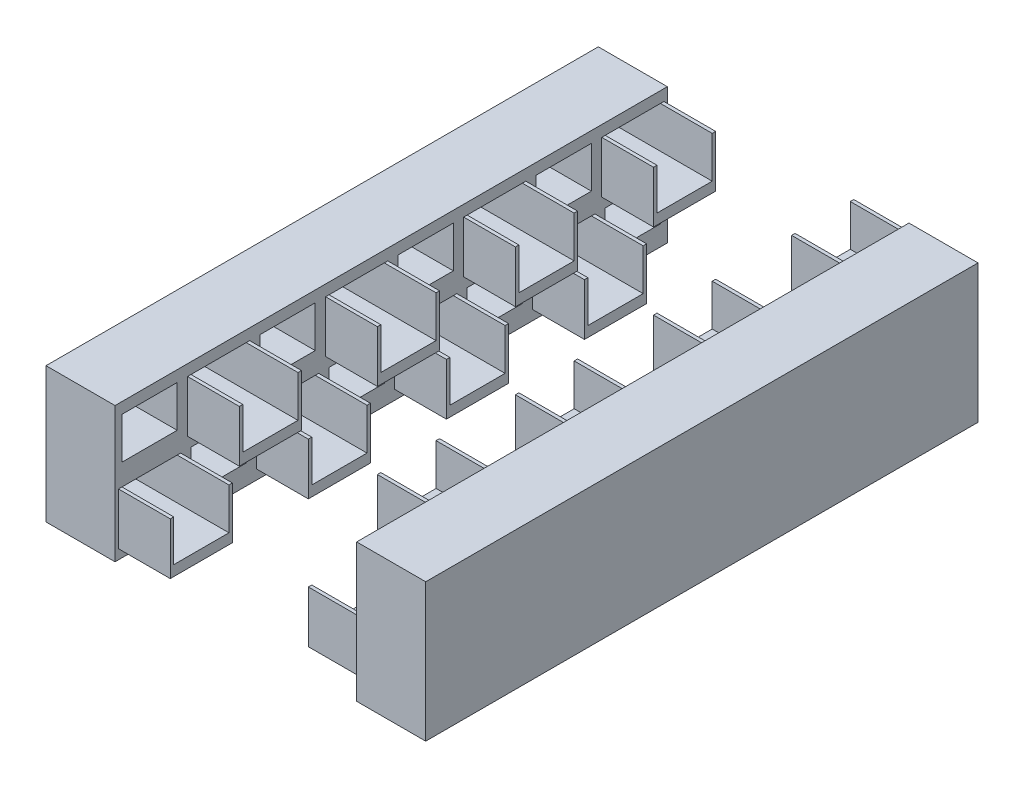
SolidWorks part; units mm, degrees
material "6061-O (SS)"
ref_plane "Alzado" through (0, 0, 0) normal (0, 0, 1) x (1, 0, 0)
ref_plane "Planta" through (0, 0, 0) normal (0, 1, 0) x (1, 0, 0)
ref_plane "Vista lateral" through (0, 0, 0) normal (1, 0, 0) x (0, 0, -1)
sketch "Sketch2" plane through (0, 0, 0) normal (1, 0, 0) x (0, 0, -1)
  line L160 (-3913.0493, 1960.5992) -> (4086.9507, 1960.5992)
  line L161 (-3913.0493, 1960.5992) -> (-3913.0493, 0)
  line L162 (-3913.0493, 0) -> (4086.9507, 0)
  line L163 (4086.9507, 1960.5992) -> (4086.9507, 0)
  line L164 (-3813.0493, 889.2792) -> (-3013.0493, 889.2792)
  line L165 (-3863.0493, 889.2792) -> (-2963.0493, 889.2792)
  line L166 (-3863.0493, 1799.9392) -> (-2963.0493, 1799.9392)
  line L167 (-3863.0493, 1799.9392) -> (-3863.0493, 1049.9392)
  line L168 (-3863.0493, 1049.9392) -> (-2963.0493, 1049.9392)
  line L169 (-2963.0493, 1799.9392) -> (-2963.0493, 1049.9392)
  line L170 (-3863.0493, 889.2792) -> (-3863.0493, 139.2792)
  line L171 (-3863.0493, 139.2792) -> (-2963.0493, 139.2792)
  line L172 (-2963.0493, 889.2792) -> (-2963.0493, 139.2792)
  line L173 (-2863.0493, 1799.9392) -> (-1963.0493, 1799.9392)
  line L174 (-2863.0493, 1799.9392) -> (-2863.0493, 1049.9392)
  line L175 (-2863.0493, 1049.9392) -> (-1963.0493, 1049.9392)
  line L176 (-1963.0493, 1799.9392) -> (-1963.0493, 1049.9392)
  line L177 (-2863.0493, 889.2792) -> (-1963.0493, 889.2792)
  line L178 (-2863.0493, 889.2792) -> (-2863.0493, 139.2792)
  line L179 (-2863.0493, 139.2792) -> (-1963.0493, 139.2792)
  line L180 (-1963.0493, 889.2792) -> (-1963.0493, 139.2792)
  line L181 (-1863.0493, 1799.9392) -> (-963.0493, 1799.9392)
  line L182 (-1863.0493, 1799.9392) -> (-1863.0493, 1049.9392)
  line L183 (-1863.0493, 1049.9392) -> (-963.0493, 1049.9392)
  line L184 (-963.0493, 1799.9392) -> (-963.0493, 1049.9392)
  line L185 (-1863.0493, 889.2792) -> (-963.0493, 889.2792)
  line L186 (-1863.0493, 889.2792) -> (-1863.0493, 139.2792)
  line L187 (-1863.0493, 139.2792) -> (-963.0493, 139.2792)
  line L188 (-963.0493, 889.2792) -> (-963.0493, 139.2792)
  line L189 (-863.0493, 1799.9392) -> (36.9507, 1799.9392)
  line L190 (-863.0493, 1799.9392) -> (-863.0493, 1049.9392)
  line L191 (-863.0493, 1049.9392) -> (36.9507, 1049.9392)
  line L192 (36.9507, 1799.9392) -> (36.9507, 1049.9392)
  line L193 (136.9507, 1799.9392) -> (1036.9507, 1799.9392)
  line L194 (136.9507, 1799.9392) -> (136.9507, 1049.9392)
  line L195 (136.9507, 1049.9392) -> (1036.9507, 1049.9392)
  line L196 (1036.9507, 1799.9392) -> (1036.9507, 1049.9392)
  line L197 (-863.0493, 889.2792) -> (36.9507, 889.2792)
  line L198 (-863.0493, 889.2792) -> (-863.0493, 139.2792)
  line L199 (-863.0493, 139.2792) -> (36.9507, 139.2792)
  line L200 (36.9507, 889.2792) -> (36.9507, 139.2792)
  line L201 (136.9507, 889.2792) -> (1036.9507, 889.2792)
  line L202 (136.9507, 889.2792) -> (136.9507, 139.2792)
  line L203 (136.9507, 139.2792) -> (1036.9507, 139.2792)
  line L204 (1036.9507, 889.2792) -> (1036.9507, 139.2792)
  line L205 (1136.9507, 1799.9392) -> (2036.9507, 1799.9392)
  line L206 (1136.9507, 1799.9392) -> (1136.9507, 1049.9392)
  line L207 (1136.9507, 1049.9392) -> (2036.9507, 1049.9392)
  line L208 (2036.9507, 1799.9392) -> (2036.9507, 1049.9392)
  line L209 (1136.9507, 889.2792) -> (2036.9507, 889.2792)
  line L210 (1136.9507, 889.2792) -> (1136.9507, 139.2792)
  line L211 (1136.9507, 139.2792) -> (2036.9507, 139.2792)
  line L212 (2036.9507, 889.2792) -> (2036.9507, 139.2792)
  line L213 (2136.9507, 1799.9392) -> (3036.9507, 1799.9392)
  line L214 (2136.9507, 1799.9392) -> (2136.9507, 1049.9392)
  line L215 (2136.9507, 1049.9392) -> (3036.9507, 1049.9392)
  line L216 (3036.9507, 1799.9392) -> (3036.9507, 1049.9392)
  line L217 (2136.9507, 889.2792) -> (3036.9507, 889.2792)
  line L218 (2136.9507, 889.2792) -> (2136.9507, 139.2792)
  line L219 (2136.9507, 139.2792) -> (3036.9507, 139.2792)
  line L220 (3036.9507, 889.2792) -> (3036.9507, 139.2792)
  line L221 (3136.9507, 889.2792) -> (4036.9507, 889.2792)
  line L222 (3136.9507, 889.2792) -> (3136.9507, 139.2792)
  line L223 (3136.9507, 139.2792) -> (4036.9507, 139.2792)
  line L224 (4036.9507, 889.2792) -> (4036.9507, 139.2792)
  line L225 (3136.9507, 1799.9392) -> (4036.9507, 1799.9392)
  line L226 (3136.9507, 1799.9392) -> (3136.9507, 1049.9392)
  line L227 (3136.9507, 1049.9392) -> (4036.9507, 1049.9392)
  line L228 (4036.9507, 1799.9392) -> (4036.9507, 1049.9392)
  line L229 (-3813.0493, 889.2792) -> (-3813.0493, 289.2792)
  line L230 (-3813.0493, 289.2792) -> (-3013.0493, 289.2792)
  line L231 (-3013.0493, 889.2792) -> (-3013.0493, 289.2792)
  line L232 (-2813.0493, 889.2792) -> (-2013.0493, 889.2792)
  line L233 (-2813.0493, 889.2792) -> (-2813.0493, 289.2792)
  line L234 (-2813.0493, 289.2792) -> (-2013.0493, 289.2792)
  line L235 (-2013.0493, 889.2792) -> (-2013.0493, 289.2792)
  line L236 (-3813.0493, 1799.9392) -> (-3013.0493, 1799.9392)
  line L237 (-3813.0493, 1799.9392) -> (-3813.0493, 1199.9392)
  line L238 (-3813.0493, 1199.9392) -> (-3013.0493, 1199.9392)
  line L239 (-3013.0493, 1799.9392) -> (-3013.0493, 1199.9392)
  line L240 (-2813.0493, 1799.9392) -> (-2013.0493, 1799.9392)
  line L241 (-2813.0493, 1799.9392) -> (-2813.0493, 1199.9392)
  line L242 (-2813.0493, 1199.9392) -> (-2013.0493, 1199.9392)
  line L243 (-2013.0493, 1799.9392) -> (-2013.0493, 1199.9392)
  line L244 (-1813.0493, 1799.9392) -> (-1013.0493, 1799.9392)
  line L245 (-1813.0493, 1799.9392) -> (-1813.0493, 1199.9392)
  line L246 (-1813.0493, 1199.9392) -> (-1013.0493, 1199.9392)
  line L247 (-1013.0493, 1799.9392) -> (-1013.0493, 1199.9392)
  line L248 (-1813.0493, 889.2792) -> (-1013.0493, 889.2792)
  line L249 (-1813.0493, 889.2792) -> (-1813.0493, 289.2792)
  line L250 (-1813.0493, 289.2792) -> (-1013.0493, 289.2792)
  line L251 (-1013.0493, 889.2792) -> (-1013.0493, 289.2792)
  line L252 (-813.0493, 889.2792) -> (-13.0493, 889.2792)
  line L253 (-813.0493, 889.2792) -> (-813.0493, 289.2792)
  line L254 (-813.0493, 289.2792) -> (-13.0493, 289.2792)
  line L255 (-13.0493, 889.2792) -> (-13.0493, 289.2792)
  line L256 (-813.0493, 1799.9392) -> (-13.0493, 1799.9392)
  line L257 (-813.0493, 1799.9392) -> (-813.0493, 1199.9392)
  line L258 (-813.0493, 1199.9392) -> (-13.0493, 1199.9392)
  line L259 (-13.0493, 1799.9392) -> (-13.0493, 1199.9392)
  line L260 (186.9507, 889.2792) -> (986.9507, 889.2792)
  line L261 (186.9507, 889.2792) -> (186.9507, 289.2792)
  line L262 (186.9507, 289.2792) -> (986.9507, 289.2792)
  line L263 (986.9507, 889.2792) -> (986.9507, 289.2792)
  line L264 (186.9507, 1799.9392) -> (986.9507, 1799.9392)
  line L265 (186.9507, 1799.9392) -> (186.9507, 1199.9392)
  line L266 (186.9507, 1199.9392) -> (986.9507, 1199.9392)
  line L267 (986.9507, 1799.9392) -> (986.9507, 1199.9392)
  line L268 (1186.9507, 1799.9392) -> (1986.9507, 1799.9392)
  line L269 (1186.9507, 1799.9392) -> (1186.9507, 1199.9392)
  line L270 (1186.9507, 1199.9392) -> (1986.9507, 1199.9392)
  line L271 (1986.9507, 1799.9392) -> (1986.9507, 1199.9392)
  line L272 (1186.9507, 889.2792) -> (1986.9507, 889.2792)
  line L273 (1186.9507, 889.2792) -> (1186.9507, 289.2792)
  line L274 (1186.9507, 289.2792) -> (1986.9507, 289.2792)
  line L275 (1986.9507, 889.2792) -> (1986.9507, 289.2792)
  line L276 (2186.9507, 1799.9392) -> (2986.9507, 1799.9392)
  line L277 (2186.9507, 1799.9392) -> (2186.9507, 1199.9392)
  line L278 (2186.9507, 1199.9392) -> (2986.9507, 1199.9392)
  line L279 (2986.9507, 1799.9392) -> (2986.9507, 1199.9392)
  line L280 (2186.9507, 889.2792) -> (2986.9507, 889.2792)
  line L281 (2186.9507, 889.2792) -> (2186.9507, 289.2792)
  line L282 (2186.9507, 289.2792) -> (2986.9507, 289.2792)
  line L283 (2986.9507, 889.2792) -> (2986.9507, 289.2792)
  line L284 (3186.9507, 1799.9392) -> (3986.9507, 1799.9392)
  line L285 (3186.9507, 1799.9392) -> (3186.9507, 1199.9392)
  line L286 (3186.9507, 1199.9392) -> (3986.9507, 1199.9392)
  line L287 (3986.9507, 1799.9392) -> (3986.9507, 1199.9392)
  line L288 (3186.9507, 889.2792) -> (3986.9507, 889.2792)
  line L289 (3186.9507, 889.2792) -> (3186.9507, 289.2792)
  line L290 (3186.9507, 289.2792) -> (3986.9507, 289.2792)
  line L291 (3986.9507, 889.2792) -> (3986.9507, 289.2792)
  point P0 (-604.7604, 139.2792)
  point P14 (-3863.0493, 514.2792)
  point P19 (-2963.0493, 1424.9392)
  point P24 (0, 0)
  point P137 (4036.9507, 514.2792)
  point P138 (0, 0)
  point P139 (-3913.0493, 0)
  point P140 (86.9507, 0)
  point P141 (-691.7111, -821.32)
  dimension "D1" = 900
  dimension "D2" = 750
  dimension "D3" = 50
  dimension "D4" = 160.66
  dimension "D5" = 50
  dimension "D6" = 160.66
  dimension "D7" = 750
  dimension "D8" = 900
  dimension "D9" = 100
  dimension "D10" = 900
  dimension "D11" = 750
  dimension "D12" = 160.66
  dimension "D13" = 750
  dimension "D14" = 900
  dimension "D15" = 160.66
  dimension "D16" = 100
  dimension "D17" = 750
  dimension "D18" = 900
  dimension "D19" = 100
  dimension "D20" = 160.66
  dimension "D21" = 750
  dimension "D22" = 900
  dimension "D23" = 160.66
  dimension "D24" = 100
  dimension "D25" = 750
  dimension "D26" = 900
  dimension "D27" = 100
  dimension "D28" = 160.66
  dimension "D29" = 900
  dimension "D30" = 750
  dimension "D31" = 100
  dimension "D32" = 160.66
  dimension "D33" = 750
  dimension "D34" = 900
  dimension "D35" = 160.66
  dimension "D36" = 100
  dimension "D37" = 900
  dimension "D38" = 750
  dimension "D39" = 160.66
  dimension "D40" = 100
  dimension "D41" = 750
  dimension "D42" = 900
  dimension "D43" = 750
  dimension "D44" = 900
  dimension "D45" = 750
  dimension "D46" = 900
  dimension "D47" = 160.66
  dimension "D48" = 100
  dimension "D49" = 100
  dimension "D50" = 160.66
  dimension "D51" = 160.66
  dimension "D52" = 100
  dimension "D53" = 900
  dimension "D54" = 750
  dimension "D55" = 900
  dimension "D56" = 750
  dimension "D57" = 900
  dimension "D58" = 750
  dimension "D59" = 100
  dimension "D60" = 160.66
  dimension "D61" = 100
  dimension "D62" = 160.66
  dimension "D63" = 100
  dimension "D64" = 160.66
  dimension "D65" = 600
  dimension "D66" = 800
  dimension "D67" = 50
  dimension "D68" = 50
  dimension "D69" = 800
  dimension "D70" = 600
  dimension "D71" = 50
  dimension "D72" = 800
  dimension "D73" = 600
  dimension "D74" = 50
  dimension "D75" = 800
  dimension "D76" = 600
  dimension "D77" = 50
  dimension "D78" = 800
  dimension "D79" = 600
  dimension "D80" = 50
  dimension "D81" = 800
  dimension "D82" = 600
  dimension "D83" = 800
  dimension "D84" = 600
  dimension "D85" = 50
  dimension "D86" = 800
  dimension "D87" = 600
  dimension "D88" = 50
  dimension "D89" = 800
  dimension "D90" = 50
  dimension "D91" = 600
  dimension "D92" = 800
  dimension "D93" = 600
  dimension "D94" = 50
  dimension "D95" = 800
  dimension "D96" = 600
  dimension "D97" = 50
  dimension "D98" = 800
  dimension "D99" = 600
  dimension "D100" = 50
  dimension "D101" = 800
  dimension "D102" = 600
  dimension "D103" = 50
  dimension "D104" = 800
  dimension "D105" = 600
  dimension "D106" = 50
  dimension "D107" = 800
  dimension "D108" = 600
  dimension "D109" = 50
  dimension "D110" = 800
  dimension "D111" = 600
  dimension "D112" = 50
  dimension "D113" = 8000
  dimension "D114" = 1960.5992
extrude "Boss-Extrude25" add sketch "Sketch2" along normal blind 1000 contours L163 L160 L161 L162 L166 L169 L168 L167 L165 L172 L171 L170 L164 L173 L176 L175 L174 L177 L180 L179 L178 L181 L184 L183 L182 L185 L188 L187 L186 L189 L192 | L166 L239 L238 L237 L167 L168 L169 | L177 L235 L234 L233 L178 L179 L180 | L181 L247 L246 L245 L182 L183 L184 | L197 L255 L254 L253 L198 L199 L200 | L193 L267 L266 L265 L194 L195 L196 | L209 L275 L274 L273 L210 L211 L212 | L213 L279 L278 L277 L214 L215 L216 | L221 L291 L290 L289 L222 L223 L224 region at (0, 1003.9355, -86.9507) region at (0, 1788.2238, 3838.0493) region at (0, 877.5638, 2838.0493) region at (0, 1788.2238, 1838.0493) region at (0, 1788.2238, -161.9507) region at (0, 877.5638, 838.0493) region at (0, 877.5638, -1161.9507) region at (0, 1788.2238, -2161.9507) region at (0, 877.5638, -3161.9507)
extrude "Boss-Extrude26" add sketch "Sketch2<31>" along normal blind 1750 contours L165 L231 L230 L229 L170 L171 L172 | L173 L243 L242 L241 L174 L175 L176 | L185 L251 L250 L249 L186 L187 L188 | L189 L259 L258 L257 L190 L191 L192 | L201 L263 L262 L261 L202 L203 L204 | L205 L271 L270 L269 L206 L207 L208 | L217 L283 L282 L281 L218 L219 L220 | L225 L287 L286 L285 L226 L227 L228 region at (0, 589.2792, 3824.7647) region at (0, 1788.2238, 2838.0493) region at (0, 877.5638, 1838.0493) region at (0, 1788.2238, 838.0493) region at (0, 877.5638, -161.9507) region at (0, 1788.2238, -1161.9507) region at (0, 877.5638, -2161.9507) region at (0, 1788.2238, -3161.9507)
sketch "Sketch2<31>" plane through (0, 0, 0) normal (1, 0, 0) x (0, 0, -1) same geometry as "Sketch2"
extrude "Boss-Extrude28" add sketch "Sketch2<33>" along normal blind 50 contours L239 L166 L237 L238 | L231 L164 L229 L230 | L243 L173 L241 L242 | L235 L177 L233 L234 | L247 L181 L245 L246 | L251 L185 L249 L250 | L259 L189 L257 L258 | L255 L197 L253 L254 | L267 L193 L265 L266 | L263 L201 L261 L262 | L271 L205 L269 L270 | L275 L209 L273 L274 | L279 L213 L277 L278 | L283 L217 L281 L282 | L287 L225 L285 L286 | L291 L221 L289 L290 region at (0, 589.2792, 3413.0493) region at (0, 1499.9392, 3413.0493) region at (0, 1499.9392, 2413.0493) region at (0, 589.2792, 2413.0493) region at (0, 1499.9392, 1413.0493) region at (0, 589.2792, 1413.0493) region at (0, 1499.9392, 413.0493) region at (0, 1499.9392, -586.9507) region at (0, 589.2792, 413.0493) region at (0, 589.2792, -586.9507) region at (0, 1499.9392, -1586.9507) region at (0, 589.2792, -1586.9507) region at (0, 1499.9392, -2586.9507) region at (0, 589.2792, -2586.9507) region at (0, 589.2792, -3586.9507) region at (0, 1499.9392, -3586.9507)
sketch "Sketch2<33>" plane through (0, 0, 0) normal (1, 0, 0) x (0, 0, -1) same geometry as "Sketch2"
sketch "Sketch12" plane through (0, 0, 0) normal (0, 1, 0) x (1, 0, 0)
  line L1 (1000, -3913.0493) -> (4500, -3913.0493)
  line L2 (1000, -3913.0493) -> (1000, 4086.9507)
  line L3 (1000, 4086.9507) -> (4500, 4086.9507)
  line L4 (4500, -3913.0493) -> (4500, 4086.9507)
  line L5 (4500, -3913.0493) -> (5500, -3913.0493)
  line L6 (4500, -3913.0493) -> (4500, 4086.9507)
  line L7 (4500, 4086.9507) -> (5500, 4086.9507)
  line L8 (5500, -3913.0493) -> (5500, 4086.9507)
  dimension "D1" = 3500
  dimension "D2" = 8000
  dimension "D3" = 1000
extrude "Boss-Extrude29" add sketch "Sketch12" along normal blind 2000 separate body contours L5 L8 L7 L4 region at (5000, 0, -86.9507)
sketch "Sketch18" plane through (5500, 0, 0) normal (1, 0, 0) x (0, 0, -1)
  line L4 (-3813.0493, 1034.7546) -> (-3013.0493, 1034.7546)
  line L5 (-3863.0493, 1034.7546) -> (-2963.0493, 1034.7546)
  line L6 (-3863.0493, 1945.4146) -> (-2963.0493, 1945.4146)
  line L7 (-3863.0493, 1945.4146) -> (-3863.0493, 1195.4146)
  line L8 (-3863.0493, 1195.4146) -> (-2963.0493, 1195.4146)
  line L9 (-2963.0493, 1945.4146) -> (-2963.0493, 1195.4146)
  line L10 (-3863.0493, 1034.7546) -> (-3863.0493, 284.7546)
  line L11 (-3863.0493, 284.7546) -> (-2963.0493, 284.7546)
  line L12 (-2963.0493, 1034.7546) -> (-2963.0493, 284.7546)
  line L13 (-2863.0493, 1945.4146) -> (-1963.0493, 1945.4146)
  line L14 (-2863.0493, 1945.4146) -> (-2863.0493, 1195.4146)
  line L15 (-2863.0493, 1195.4146) -> (-1963.0493, 1195.4146)
  line L16 (-1963.0493, 1945.4146) -> (-1963.0493, 1195.4146)
  line L17 (-2863.0493, 1034.7546) -> (-1963.0493, 1034.7546)
  line L18 (-2863.0493, 1034.7546) -> (-2863.0493, 284.7546)
  line L19 (-2863.0493, 284.7546) -> (-1963.0493, 284.7546)
  line L20 (-1963.0493, 1034.7546) -> (-1963.0493, 284.7546)
  line L21 (-1863.0493, 1945.4146) -> (-963.0493, 1945.4146)
  line L22 (-1863.0493, 1945.4146) -> (-1863.0493, 1195.4146)
  line L23 (-1863.0493, 1195.4146) -> (-963.0493, 1195.4146)
  line L24 (-963.0493, 1945.4146) -> (-963.0493, 1195.4146)
  line L25 (-1863.0493, 1034.7546) -> (-963.0493, 1034.7546)
  line L26 (-1863.0493, 1034.7546) -> (-1863.0493, 284.7546)
  line L27 (-1863.0493, 284.7546) -> (-963.0493, 284.7546)
  line L28 (-963.0493, 1034.7546) -> (-963.0493, 284.7546)
  line L29 (-863.0493, 1945.4146) -> (36.9507, 1945.4146)
  line L30 (-863.0493, 1945.4146) -> (-863.0493, 1195.4146)
  line L31 (-863.0493, 1195.4146) -> (36.9507, 1195.4146)
  line L32 (36.9507, 1945.4146) -> (36.9507, 1195.4146)
  line L33 (136.9507, 1945.4146) -> (1036.9507, 1945.4146)
  line L34 (136.9507, 1945.4146) -> (136.9507, 1195.4146)
  line L35 (136.9507, 1195.4146) -> (1036.9507, 1195.4146)
  line L36 (1036.9507, 1945.4146) -> (1036.9507, 1195.4146)
  line L37 (-863.0493, 1034.7546) -> (36.9507, 1034.7546)
  line L38 (-863.0493, 1034.7546) -> (-863.0493, 284.7546)
  line L39 (-863.0493, 284.7546) -> (36.9507, 284.7546)
  line L40 (36.9507, 1034.7546) -> (36.9507, 284.7546)
  line L41 (136.9507, 1034.7546) -> (1036.9507, 1034.7546)
  line L42 (136.9507, 1034.7546) -> (136.9507, 284.7546)
  line L43 (136.9507, 284.7546) -> (1036.9507, 284.7546)
  line L44 (1036.9507, 1034.7546) -> (1036.9507, 284.7546)
  line L45 (1136.9507, 1945.4146) -> (2036.9507, 1945.4146)
  line L46 (1136.9507, 1945.4146) -> (1136.9507, 1195.4146)
  line L47 (1136.9507, 1195.4146) -> (2036.9507, 1195.4146)
  line L48 (2036.9507, 1945.4146) -> (2036.9507, 1195.4146)
  line L49 (1136.9507, 1034.7546) -> (2036.9507, 1034.7546)
  line L50 (1136.9507, 1034.7546) -> (1136.9507, 284.7546)
  line L51 (1136.9507, 284.7546) -> (2036.9507, 284.7546)
  line L52 (2036.9507, 1034.7546) -> (2036.9507, 284.7546)
  line L53 (2136.9507, 1945.4146) -> (3036.9507, 1945.4146)
  line L54 (2136.9507, 1945.4146) -> (2136.9507, 1195.4146)
  line L55 (2136.9507, 1195.4146) -> (3036.9507, 1195.4146)
  line L56 (3036.9507, 1945.4146) -> (3036.9507, 1195.4146)
  line L57 (2136.9507, 1034.7546) -> (3036.9507, 1034.7546)
  line L58 (2136.9507, 1034.7546) -> (2136.9507, 284.7546)
  line L59 (2136.9507, 284.7546) -> (3036.9507, 284.7546)
  line L60 (3036.9507, 1034.7546) -> (3036.9507, 284.7546)
  line L61 (3136.9507, 1034.7546) -> (4036.9507, 1034.7546)
  line L62 (3136.9507, 1034.7546) -> (3136.9507, 284.7546)
  line L63 (3136.9507, 284.7546) -> (4036.9507, 284.7546)
  line L64 (4036.9507, 1034.7546) -> (4036.9507, 284.7546)
  line L65 (3136.9507, 1945.4146) -> (4036.9507, 1945.4146)
  line L66 (3136.9507, 1945.4146) -> (3136.9507, 1195.4146)
  line L67 (3136.9507, 1195.4146) -> (4036.9507, 1195.4146)
  line L68 (4036.9507, 1945.4146) -> (4036.9507, 1195.4146)
  line L69 (-3813.0493, 1034.7546) -> (-3813.0493, 434.7546)
  line L70 (-3813.0493, 434.7546) -> (-3013.0493, 434.7546)
  line L71 (-3013.0493, 1034.7546) -> (-3013.0493, 434.7546)
  line L72 (-2813.0493, 1034.7546) -> (-2013.0493, 1034.7546)
  line L73 (-2813.0493, 1034.7546) -> (-2813.0493, 434.7546)
  line L74 (-2813.0493, 434.7546) -> (-2013.0493, 434.7546)
  line L75 (-2013.0493, 1034.7546) -> (-2013.0493, 434.7546)
  line L76 (-3813.0493, 1945.4146) -> (-3013.0493, 1945.4146)
  line L77 (-3813.0493, 1945.4146) -> (-3813.0493, 1345.4146)
  line L78 (-3813.0493, 1345.4146) -> (-3013.0493, 1345.4146)
  line L79 (-3013.0493, 1945.4146) -> (-3013.0493, 1345.4146)
  line L80 (-2813.0493, 1945.4146) -> (-2013.0493, 1945.4146)
  line L81 (-2813.0493, 1945.4146) -> (-2813.0493, 1345.4146)
  line L82 (-2813.0493, 1345.4146) -> (-2013.0493, 1345.4146)
  line L83 (-2013.0493, 1945.4146) -> (-2013.0493, 1345.4146)
  line L84 (-1813.0493, 1945.4146) -> (-1013.0493, 1945.4146)
  line L85 (-1813.0493, 1945.4146) -> (-1813.0493, 1345.4146)
  line L86 (-1813.0493, 1345.4146) -> (-1013.0493, 1345.4146)
  line L87 (-1013.0493, 1945.4146) -> (-1013.0493, 1345.4146)
  line L88 (-1813.0493, 1034.7546) -> (-1013.0493, 1034.7546)
  line L89 (-1813.0493, 1034.7546) -> (-1813.0493, 434.7546)
  line L90 (-1813.0493, 434.7546) -> (-1013.0493, 434.7546)
  line L91 (-1013.0493, 1034.7546) -> (-1013.0493, 434.7546)
  line L92 (-813.0493, 1034.7546) -> (-13.0493, 1034.7546)
  line L93 (-813.0493, 1034.7546) -> (-813.0493, 434.7546)
  line L94 (-813.0493, 434.7546) -> (-13.0493, 434.7546)
  line L95 (-13.0493, 1034.7546) -> (-13.0493, 434.7546)
  line L96 (-813.0493, 1945.4146) -> (-13.0493, 1945.4146)
  line L97 (-813.0493, 1945.4146) -> (-813.0493, 1345.4146)
  line L98 (-813.0493, 1345.4146) -> (-13.0493, 1345.4146)
  line L99 (-13.0493, 1945.4146) -> (-13.0493, 1345.4146)
  line L100 (186.9507, 1034.7546) -> (986.9507, 1034.7546)
  line L101 (186.9507, 1034.7546) -> (186.9507, 434.7546)
  line L102 (186.9507, 434.7546) -> (986.9507, 434.7546)
  line L103 (986.9507, 1034.7546) -> (986.9507, 434.7546)
  line L104 (186.9507, 1945.4146) -> (986.9507, 1945.4146)
  line L105 (186.9507, 1945.4146) -> (186.9507, 1345.4146)
  line L106 (186.9507, 1345.4146) -> (986.9507, 1345.4146)
  line L107 (986.9507, 1945.4146) -> (986.9507, 1345.4146)
  line L108 (1186.9507, 1945.4146) -> (1986.9507, 1945.4146)
  line L109 (1186.9507, 1945.4146) -> (1186.9507, 1345.4146)
  line L110 (1186.9507, 1345.4146) -> (1986.9507, 1345.4146)
  line L111 (1986.9507, 1945.4146) -> (1986.9507, 1345.4146)
  line L112 (1186.9507, 1034.7546) -> (1986.9507, 1034.7546)
  line L113 (1186.9507, 1034.7546) -> (1186.9507, 434.7546)
  line L114 (1186.9507, 434.7546) -> (1986.9507, 434.7546)
  line L115 (1986.9507, 1034.7546) -> (1986.9507, 434.7546)
  line L116 (2186.9507, 1945.4146) -> (2986.9507, 1945.4146)
  line L117 (2186.9507, 1945.4146) -> (2186.9507, 1345.4146)
  line L118 (2186.9507, 1345.4146) -> (2986.9507, 1345.4146)
  line L119 (2986.9507, 1945.4146) -> (2986.9507, 1345.4146)
  line L120 (2186.9507, 1034.7546) -> (2986.9507, 1034.7546)
  line L121 (2186.9507, 1034.7546) -> (2186.9507, 434.7546)
  line L122 (2186.9507, 434.7546) -> (2986.9507, 434.7546)
  line L123 (2986.9507, 1034.7546) -> (2986.9507, 434.7546)
  line L124 (3186.9507, 1945.4146) -> (3986.9507, 1945.4146)
  line L125 (3186.9507, 1945.4146) -> (3186.9507, 1345.4146)
  line L126 (3186.9507, 1345.4146) -> (3986.9507, 1345.4146)
  line L127 (3986.9507, 1945.4146) -> (3986.9507, 1345.4146)
  line L128 (3186.9507, 1034.7546) -> (3986.9507, 1034.7546)
  line L129 (3186.9507, 1034.7546) -> (3186.9507, 434.7546)
  line L130 (3186.9507, 434.7546) -> (3986.9507, 434.7546)
  line L131 (3986.9507, 1034.7546) -> (3986.9507, 434.7546)
  line L132 (-3913.0493, 2000) -> (-3913.0493, 0) construction
  point P0 (-604.7604, 284.7546)
  point P18 (-2963.0493, 1570.4146)
  point P135 (4036.9507, 659.7546)
  point P136 (-3870.7737, 145.4755)
  point P137 (129.2263, 145.4755)
  dimension "D1" = 900
  dimension "D2" = 750
  dimension "D6" = 160.66
  dimension "D7" = 750
  dimension "D8" = 900
  dimension "D9" = 100
  dimension "D10" = 900
  dimension "D11" = 750
  dimension "D12" = 50
  dimension "D13" = 750
  dimension "D14" = 900
  dimension "D15" = 160.66
  dimension "D16" = 100
  dimension "D17" = 750
  dimension "D18" = 900
  dimension "D19" = 100
  dimension "D21" = 750
  dimension "D22" = 900
  dimension "D23" = 160.66
  dimension "D24" = 100
  dimension "D25" = 750
  dimension "D26" = 900
  dimension "D27" = 100
  dimension "D29" = 900
  dimension "D30" = 750
  dimension "D31" = 100
  dimension "D33" = 750
  dimension "D34" = 900
  dimension "D35" = 160.66
  dimension "D36" = 100
  dimension "D37" = 900
  dimension "D38" = 750
  dimension "D39" = 160.66
  dimension "D40" = 100
  dimension "D41" = 750
  dimension "D42" = 900
  dimension "D43" = 750
  dimension "D44" = 900
  dimension "D45" = 750
  dimension "D46" = 900
  dimension "D48" = 100
  dimension "D49" = 100
  dimension "D50" = 160.66
  dimension "D52" = 100
  dimension "D53" = 900
  dimension "D54" = 750
  dimension "D55" = 900
  dimension "D56" = 750
  dimension "D57" = 900
  dimension "D58" = 750
  dimension "D59" = 100
  dimension "D61" = 100
  dimension "D62" = 160.66
  dimension "D63" = 100
  dimension "D64" = 160.66
  dimension "D65" = 600
  dimension "D66" = 800
  dimension "D67" = 50
  dimension "D68" = 50
  dimension "D69" = 800
  dimension "D70" = 600
  dimension "D71" = 50
  dimension "D72" = 800
  dimension "D73" = 600
  dimension "D74" = 50
  dimension "D75" = 800
  dimension "D76" = 600
  dimension "D77" = 50
  dimension "D78" = 800
  dimension "D79" = 600
  dimension "D80" = 50
  dimension "D81" = 800
  dimension "D82" = 600
  dimension "D83" = 800
  dimension "D84" = 600
  dimension "D85" = 50
  dimension "D86" = 800
  dimension "D87" = 600
  dimension "D88" = 50
  dimension "D89" = 800
  dimension "D90" = 50
  dimension "D91" = 600
  dimension "D92" = 800
  dimension "D93" = 600
  dimension "D94" = 50
  dimension "D95" = 800
  dimension "D96" = 600
  dimension "D97" = 50
  dimension "D98" = 800
  dimension "D99" = 600
  dimension "D100" = 50
  dimension "D101" = 800
  dimension "D102" = 600
  dimension "D103" = 50
  dimension "D104" = 800
  dimension "D105" = 600
  dimension "D106" = 50
  dimension "D107" = 800
  dimension "D108" = 600
  dimension "D109" = 50
  dimension "D110" = 800
  dimension "D111" = 600
  dimension "D112" = 50
extrude "Boss-Extrude30" add sketch "Sketch18" against normal blind 1000 contours L6 L79 L78 L77 L7 L8 L9 | L17 L75 L74 L73 L18 L19 L20 | L21 L87 L86 L85 L22 L23 L24 | L37 L95 L94 L93 L38 L39 L40 | L33 L107 L106 L105 L34 L35 L36 | L49 L115 L114 L113 L50 L51 L52 | L53 L119 L118 L117 L54 L55 L56 | L61 L131 L130 L129 L62 L63 L64 region at (5500, 1933.6993, 3838.0493) region at (5500, 1023.0393, 2838.0493) region at (5500, 1933.6993, 1838.0493) region at (5500, 1933.6993, -161.9507) region at (5500, 1023.0393, 838.0493) region at (5500, 1023.0393, -1161.9507) region at (5500, 1933.6993, -2161.9507) region at (5500, 1023.0393, -3161.9507)
extrude "Boss-Extrude31" add sketch "Sketch18<4>" against normal blind 1750 contours L5 L71 L70 L69 L10 L11 L12 | L13 L83 L82 L81 L14 L15 L16 | L25 L91 L90 L89 L26 L27 L28 | L29 L99 L98 L97 L30 L31 L32 | L41 L103 L102 L101 L42 L43 L44 | L45 L111 L110 L109 L46 L47 L48 | L57 L123 L122 L121 L58 L59 L60 | L65 L127 L126 L125 L66 L67 L68 region at (5500, 734.7546, 3824.7647) region at (5500, 1933.6993, 2838.0493) region at (5500, 1023.0393, 1838.0493) region at (5500, 1933.6993, 838.0493) region at (5500, 1023.0393, -161.9507) region at (5500, 1933.6993, -1161.9507) region at (5500, 1023.0393, -2161.9507) region at (5500, 1933.6993, -3161.9507)
sketch "Sketch18<4>" plane through (5500, 0, 0) normal (1, 0, 0) x (0, 0, -1) same geometry as "Sketch18"
extrude "Cut-Extrude1" cut sketch "Sketch18<7>" against normal blind 1000 contours L79 L6 L77 L78 | L71 L4 L69 L70 | L83 L13 L81 L82 | L75 L17 L73 L74 | L87 L21 L85 L86 | L91 L25 L89 L90 | L99 L29 L97 L98 | L95 L37 L93 L94 | L103 L41 L101 L102 | L107 L33 L105 L106 | L115 L49 L113 L114 | L111 L45 L109 L110 | L119 L53 L117 L118 | L123 L57 L121 L122 | L127 L65 L125 L126 | L131 L61 L129 L130 region at (5500, 734.7546, 3413.0493) region at (5500, 1645.4146, 3413.0493) region at (5500, 1645.4146, 2413.0493) region at (5500, 734.7546, 2413.0493) region at (5500, 1645.4146, 1413.0493) region at (5500, 734.7546, 1413.0493) region at (5500, 1645.4146, 413.0493) region at (5500, 1645.4146, -586.9507) region at (5500, 734.7546, 413.0493) region at (5500, 734.7546, -586.9507) region at (5500, 1645.4146, -1586.9507) region at (5500, 734.7546, -1586.9507) region at (5500, 1645.4146, -2586.9507) region at (5500, 734.7546, -2586.9507) region at (5500, 734.7546, -3586.9507) region at (5500, 1645.4146, -3586.9507)
sketch "Sketch18<7>" plane through (5500, 0, 0) normal (1, 0, 0) x (0, 0, -1) same geometry as "Sketch18"
extrude "Boss-Extrude33" add sketch "Sketch18<8>" against normal blind 50 contours L79 L6 L77 L78 | L83 L13 L81 L82 | L87 L21 L85 L86 | L99 L29 L97 L98 | L95 L37 L93 L94 | L91 L25 L89 L90 | L75 L17 L73 L74 | L71 L4 L69 L70 | L107 L33 L105 L106 | L103 L41 L101 L102 | L111 L45 L109 L110 | L115 L49 L113 L114 | L119 L53 L117 L118 | L123 L57 L121 L122 | L127 L65 L125 L126 | L131 L61 L129 L130 region at (5500, 734.7546, 3413.0493) region at (5500, 1645.4146, 3413.0493) region at (5500, 1645.4146, 2413.0493) region at (5500, 734.7546, 2413.0493) region at (5500, 1645.4146, 1413.0493) region at (5500, 734.7546, 1413.0493) region at (5500, 1645.4146, 413.0493) region at (5500, 1645.4146, -586.9507) region at (5500, 734.7546, 413.0493) region at (5500, 734.7546, -586.9507) region at (5500, 1645.4146, -1586.9507) region at (5500, 734.7546, -1586.9507) region at (5500, 1645.4146, -2586.9507) region at (5500, 734.7546, -2586.9507) region at (5500, 734.7546, -3586.9507) region at (5500, 1645.4146, -3586.9507)
sketch "Sketch18<8>" plane through (5500, 0, 0) normal (1, 0, 0) x (0, 0, -1) same geometry as "Sketch18"
equation "\"50P\"= 72.9036"
